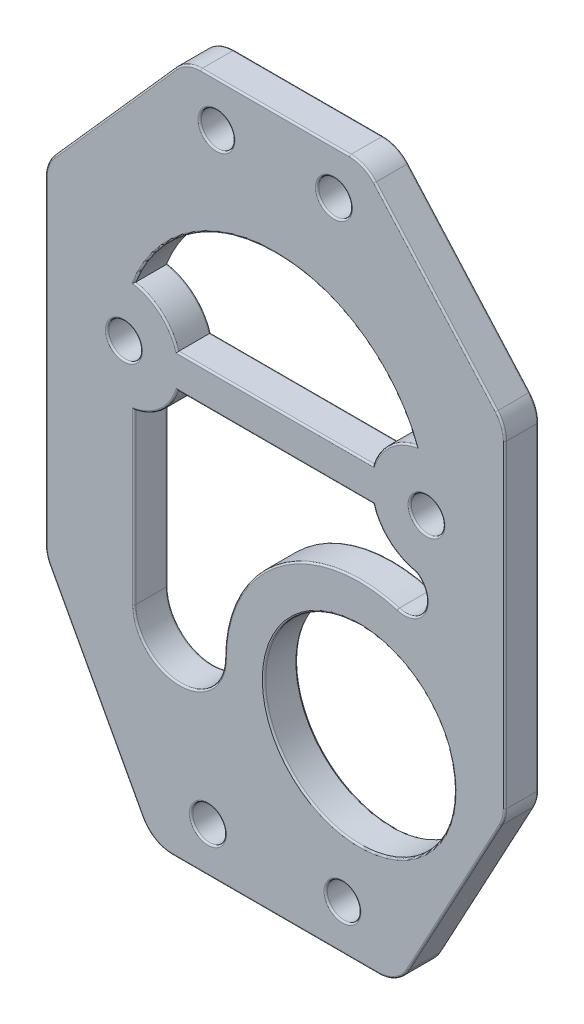
SolidWorks part; units mm, degrees
ref_plane "Front Plane" through (0, 0, 0) normal (0, 0, 1) x (1, 0, 0)
ref_plane "Top Plane" through (0, 0, 0) normal (0, 1, 0) x (1, 0, 0)
ref_plane "Right Plane" through (0, 0, 0) normal (1, 0, 0) x (0, 0, -1)
sketch "Sketch1" plane through (0, 0, 0) normal (0, 0, 1) x (1, 0, 0)
  line L0 (0, 0) -> (0, 62) construction
  line L1 (7.9898, 62) -> (-7.9898, 62)
  line L2 (-7.9898, 62) -> (-20.5, 47.8997)
  line L3 (-20.5, 47.8997) -> (-20.5, 17.5997)
  line L4 (-20.5, 17.5997) -> (-11, 0)
  line L5 (-11, 0) -> (0, 0)
  line L6 (20.5, 17.5997) -> (11, 0)
  line L7 (20.5, 47.8997) -> (20.5, 17.5997)
  line L8 (7.9898, 62) -> (20.5, 47.8997)
  line L9 (-13.5, 37.5997) -> (13.5, 37.5997) construction
  line L10 (-8.7303, 39.0997) -> (8.7303, 39.0997)
  line L11 (8.7303, 36.0997) -> (-8.7303, 36.0997) construction
  line L12 (8.7303, 36.0997) -> (8.7303, 39.0997) construction
  line L13 (8.7303, 39.0997) -> (-8.7303, 39.0997) construction
  line L14 (-8.7303, 36.0997) -> (-8.7303, 39.0997) construction
  line L15 (8.7303, 36.0997) -> (-8.7303, 39.0997) construction
  line L16 (8.7303, 39.0997) -> (-8.7303, 36.0997) construction
  line L17 (-8.7303, 36.0997) -> (8.7303, 36.0997)
  line L18 (13.5, 37.5997) -> (7.5, 17.5997) construction
  line L19 (-12.5741, 32.6862) -> (-12.5741, 17.5997)
  line L20 (11, 0) -> (-11, 0)
  circle A0 centre (-5.2398, 58) radius 1.5
  circle A1 centre (-13.5, 37.5997) radius 1.5
  circle A2 centre (-6, 4) radius 1.5
  circle A3 centre (6, 4) radius 1.5
  circle A4 centre (13.5, 37.5997) radius 1.5
  circle A5 centre (5.2398, 58) radius 1.5
  circle A6 centre (7.5, 17.5997) radius 8.5
  circle A7 centre (13.5, 37.5997) radius 5 construction
  circle A8 centre (-13.5, 37.5997) radius 5 construction
  circle A9 centre (7.5, 17.5997) radius 12 construction
  arc A10 (-12.5741, 42.5132) -> (12.5741, 42.5132) centre (0, 37.5997) cw
  arc A11 (-12.5741, 42.5132) -> (-8.7303, 39.0997) centre (-13.5, 37.5997) cw
  arc A12 (8.7303, 39.0997) -> (12.5741, 42.5132) centre (13.5, 37.5997) cw
  arc A13 (-8.7303, 36.0997) -> (-12.5741, 32.6862) centre (-13.5, 37.5997) cw
  arc A14 (8.7303, 36.0997) -> (12.5741, 32.6862) centre (13.5, 37.5997) ccw
  arc A17 (-12.5741, 17.5997) -> (-4.5, 17.5997) centre (-8.537, 17.5997) ccw
  arc A18 (12.5741, 32.6862) -> (10.9482, 29.0936) centre (11.5198, 30.9991) cw
  arc A19 (10.9482, 29.0936) -> (-4.5, 17.5997) centre (7.5, 17.5997) ccw
  dimension "D12" = 3
  dimension "D14" = 17
  dimension "D19" = 13.5
  dimension "D1" = 62
  dimension "D2" = 18.85
  dimension "D3" = 30.3
  dimension "D4" = 20
  dimension "D5" = 11
  dimension "D6" = 20.5
  dimension "D7" = 4
  dimension "D8" = 2.75
  dimension "D9" = 10.3
  dimension "D10" = 6
  dimension "D11" = 4
  dimension "D13" = 7
  dimension "D15" = 13
  dimension "D20" = 3
  dimension "D16" = 3.5
  dimension "D17" = 3.5
  dimension "D18" = 3.5
extrude "Boss-Extrude1" add sketch "Sketch1" along normal blind 3 contours L20 L6 L7 L8 L1 L2 L3 L4 L5 A12 L10 A11 A10 A6 A4 A0 A1 A2 A3 A5 A18 A19 A17 L19 A13 L17 A14 region at (13.6889, 54.4565, 0)
fillet "Fillet1" radius 3 8 edges at (-11, 0, 1.5) (-20.5, 17.5997, 1.5) (-20.5, 47.8997, 1.5) (-7.9898, 62, 1.5) (7.9898, 62, 1.5) (20.5, 47.8997, 1.5) (11, 0, 1.5) (20.5, 17.5997, 1.5)
fillet "Fillet2" radius 0.15 68 edges at (10.1799, 33.8611, 3) (0, 36.0997, 3) (-10.1799, 33.8611, 3) (-12.5741, 25.143, 3) (-8.537, 13.5627, 3) (0.3368, 27.2272, 3) (13.3322, 30.1789, 3) (6.7398, 58, 3) (7.5, 4, 3) (-4.5, 4, 3) (-12, 37.5997, 3) (-3.7398, 58, 3) (-20.4086, 17.6228, 3) (-20.5, 32.5592, 3) (-20.3047, 47.8256, 3) (-14.3146, 54.8714, 3) (-7.8712, 61.7361, 3) (0, 62, 3) (7.8712, 61.7361, 3) (14.3146, 54.8714, 3) (20.3047, 47.8256, 3) (20.5, 32.5592, 3) (20.4086, 17.6228, 3) (15.9951, 9.2539, 3) (10.7472, 0.4237, 3) (0, 0, 3) (-10.7472, 0.4237, 3) (-15.9951, 9.2539, 3) (15, 37.5997, 3) (16, 17.5997, 3) (0, 51.0997, 3) (-10.1799, 41.3383, 3) (0, 39.0997, 3) (10.1799, 41.3383, 3) (0.3368, 27.2272, 0) (-8.537, 13.5627, 0) (-12.5741, 25.143, 0) (-10.1799, 33.8611, 0) (0, 36.0997, 0) (10.1799, 33.8611, 0) (13.3322, 30.1789, 0) (6.7398, 58, 0) (7.5, 4, 0) (-4.5, 4, 0) (-12, 37.5997, 0) (-3.7398, 58, 0) (10.7472, 0.4237, 0) (15.9951, 9.2539, 0) (20.4086, 17.6228, 0) (20.5, 32.5592, 0) (20.3047, 47.8256, 0) (14.3146, 54.8714, 0) (7.8712, 61.7361, 0) (0, 62, 0) (-7.8712, 61.7361, 0) (-14.3146, 54.8714, 0) (-20.3047, 47.8256, 0) (-20.5, 32.5592, 0) (-20.4086, 17.6228, 0) (-15.9951, 9.2539, 0) (-10.7472, 0.4237, 0) (0, 0, 0) (15, 37.5997, 0) (16, 17.5997, 0) (0, 39.0997, 0) (-10.1799, 41.3383, 0) (0, 51.0997, 0) (10.1799, 41.3383, 0)
